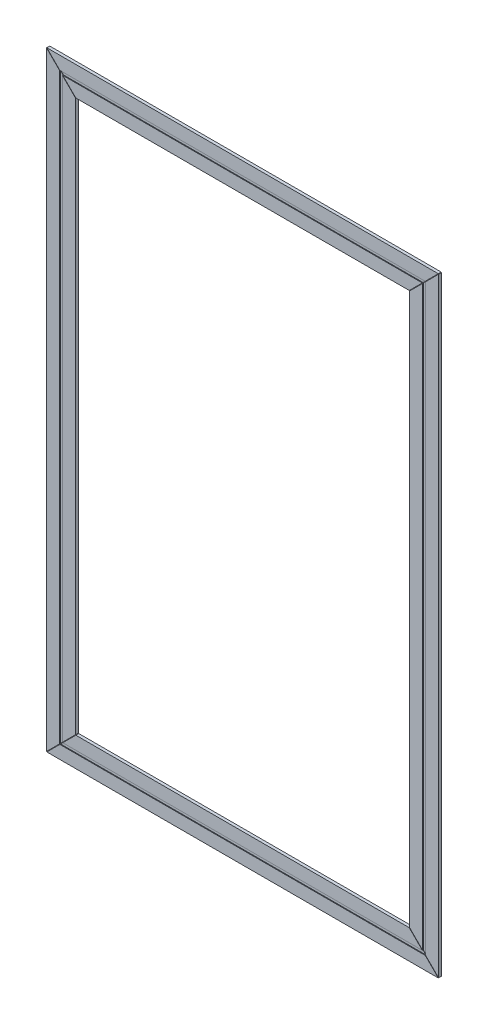
SolidWorks part; units mm, degrees
ref_plane "Front Plane" through (0, 0, 0) normal (0, 0, 1) x (1, 0, 0)
ref_plane "Top Plane" through (0, 0, 0) normal (0, 1, 0) x (1, 0, 0)
ref_plane "Right Plane" through (0, 0, 0) normal (1, 0, 0) x (0, 0, -1)
sketch "Croquis1" plane through (0, 0, 0) normal (0, 0, 1) x (1, 0, 0)
  line L0 (-115, -190) -> (-115, 190)
  line L1 (-115, -190) -> (115, -190)
  line L2 (-115, 190) -> (115, 190)
  line L3 (115, -190) -> (115, 190)
  line L4 (-115, -190) -> (115, 190) construction
  line L5 (-115, 190) -> (115, -190) construction
  line L6 (-135, -210) -> (-135, 210)
  line L7 (-135, -210) -> (135, -210)
  line L8 (-135, 210) -> (135, 210)
  line L9 (135, -210) -> (135, 210)
  line L10 (-135, -210) -> (135, 210) construction
  line L11 (-135, 210) -> (135, -210) construction
  line L12 (-135, -210) -> (-115, -190)
  line L13 (115, -190) -> (135, -210)
  line L14 (115, 190) -> (135, 210)
  line L15 (-115, 190) -> (-135, 210)
  line L16 (-125, -200) -> (-125, 200)
  line L17 (-125, 200) -> (125, 200)
  line L18 (125, 200) -> (125, -200)
  line L19 (125, -200) -> (-125, -200)
  line L20 (124, 199) -> (124, -199)
  line L21 (124, 199) -> (-124, 199)
  line L22 (124, -199) -> (-124, -199)
  line L23 (-124, 199) -> (-124, -199)
  line L24 (124, 199) -> (-124, -199) construction
  line L25 (124, -199) -> (-124, 199) construction
  line L26 (126, 201) -> (126, -201)
  line L27 (126, 201) -> (-126, 201)
  line L28 (126, -201) -> (-126, -201)
  line L29 (-126, 201) -> (-126, -201)
  line L30 (126, 201) -> (-126, -201) construction
  line L31 (126, -201) -> (-126, 201) construction
  point P1 (0, 0)
  point P2 (0, 0)
  point P16 (0, 0)
  point P17 (0, 0)
  dimension "D1" = 20
  dimension "D2" = 20
  dimension "D3" = 230
  dimension "D4" = 380
  dimension "D5" = 1
  dimension "D6" = 1
  dimension "D7" = 1
  dimension "D8" = 1
extrude "Saliente-Extruir1" add sketch "Croquis1" along normal blind 2 contours L15 L23 L12 L0 | L29 L15 L6 L12 | L27 L14 L8 L15 | L14 L21 L15 L2 | L20 L14 L3 L13 | L14 L26 L13 L9 | L13 L28 L12 L7 | L22 L13 L1 L12 region at (-119.5347, 0, 0) region at (0, -194.5565, 0) region at (0, 194.5565, 0) region at (119.5347, 0, 0) region at (0, -205.5517, 0) region at (-130.5328, 0, 0) region at (0, 205.5517, 0) region at (130.5328, 0, 0)
extrude "Saliente-Extruir2" add sketch "Croquis1<3>" along normal blind 1.5 contours L23 L15 L16 L12 | L15 L29 L12 L16 | L21 L14 L17 L15 | L14 L27 L15 L17 | L13 L22 L12 L19 | L28 L13 L19 L12 | L14 L20 L13 L18 | L26 L14 L18 L13 region at (0, -199.5007, 0) region at (-124.5004, 0, 0) region at (0, 199.5007, 0) region at (124.5004, 0, 0) region at (0, -200.5007, 0) region at (-125.5004, 0, 0) region at (0, 200.5007, 0) region at (125.5004, 0, 0)
sketch "Croquis1<3>" plane through (0, 0, 0) normal (0, 0, 1) x (1, 0, 0) same geometry as "Croquis1"
sketch "Croquis2" plane through (0, 0, 2) normal (0, 0, 1) x (1, 0, 0)
  line L0 (-115, 189.8) -> (-135, 209.8)
  line L1 (-115, -190) -> (-115, 190) construction
  line L2 (-135, -210) -> (-135, 210) construction
  line L3 (-135, 209.8) -> (-135, 210)
  line L4 (-135, 210) -> (135, 210) construction
  line L5 (-135, 210) -> (-134.8, 210)
  line L6 (-134.8, 210) -> (-114.8, 190)
  line L7 (-115, 190) -> (115, 190) construction
  line L8 (-114.8, 190) -> (-115, 190)
  line L9 (-115, 190) -> (-115, 189.8)
  line L10 (0, 0) -> (0, 168.7335) construction
  line L11 (0, 0) -> (-128.9124, 0) construction
  line L12 (115, 190) -> (115, 189.8)
  line L13 (114.8, 190) -> (115, 190)
  line L14 (134.8, 210) -> (114.8, 190)
  line L15 (135, 210) -> (134.8, 210)
  line L16 (135, 209.8) -> (135, 210)
  line L17 (115, 189.8) -> (135, 209.8)
  line L18 (115, -189.8) -> (135, -209.8)
  line L19 (135, -209.8) -> (135, -210)
  line L20 (135, -210) -> (134.8, -210)
  line L21 (134.8, -210) -> (114.8, -190)
  line L22 (114.8, -190) -> (115, -190)
  line L23 (115, -190) -> (115, -189.8)
  line L24 (-115, -190) -> (-115, -189.8)
  line L25 (-114.8, -190) -> (-115, -190)
  line L26 (-134.8, -210) -> (-114.8, -190)
  line L27 (-135, -210) -> (-134.8, -210)
  line L28 (-135, -209.8) -> (-135, -210)
  line L29 (-115, -189.8) -> (-135, -209.8)
  dimension "D1" = 0.2
  dimension "D2" = 0.2
  dimension "D3" = 0.2
  dimension "D4" = 0.2
extrude "Cortar-Extruir1" cut sketch "Croquis2" against normal blind 21
